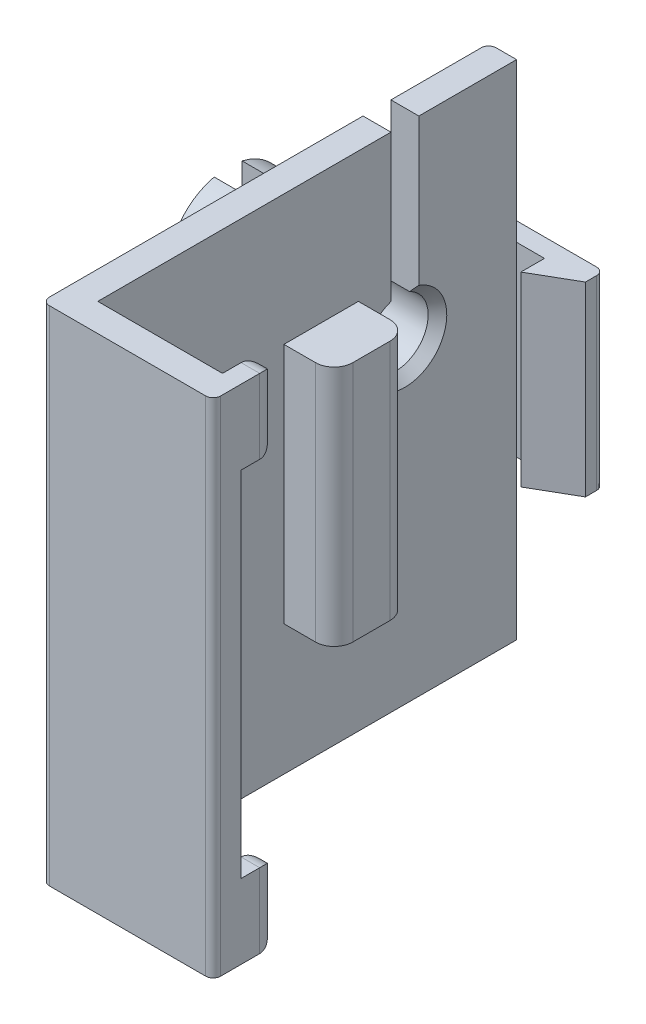
SolidWorks part; units mm, degrees
ref_plane "Front Plane" through (0, 0, 0) normal (0, 0, 1) x (1, 0, 0)
ref_plane "Top Plane" through (0, 0, 0) normal (0, 1, 0) x (1, 0, 0)
ref_plane "Right Plane" through (0, 0, 0) normal (1, 0, 0) x (0, 0, -1)
sketch "Sketch1" plane through (0, 0, 0) normal (0, 1, 0) x (1, 0, 0)
  line L0 (0, 0) -> (-2.2, 0)
  line L5 (-2.2, 0) -> (-2.2, -1.2702)
  line L6 (-2.2, -1.2702) -> (0, 0)
  dimension "D1" = 60
  dimension "D2" = 2.2
extrude "Boss-Extrude1" add sketch "Sketch1" along normal blind 5 and the other way blind 5
sketch "Sketch2" plane through (0, 0, 0) normal (0, 0, -1) x (-1, 0, 0)
  line L0 (0, 5) -> (2.2, 5) construction
  line L1 (0, -5) -> (3.7, -5)
  line L2 (0, -5) -> (0, 5)
  line L3 (0, 5) -> (3.7, 5)
  line L4 (3.7, -5) -> (3.7, 5)
  line L5 (0, -5) -> (3.7, 5) construction
  line L6 (0, 5) -> (3.7, -5) construction
  line L7 (2.2, -5) -> (2.2, 5) construction
  point P4 (1.85, 0)
  dimension "D1" = 1.5
extrude "Boss-Extrude2" add sketch "Sketch2" along normal blind 1
sketch "Sketch3" plane through (-3.7, 0, 0) normal (-1, 0, 0) x (0, 0, 1)
  line L0 (0, 0) -> (12.5427, 0) construction
  line L1 (0, -13.5) -> (22.5, -13.5)
  line L2 (0, -13.5) -> (0, 13.5)
  line L3 (0, 13.5) -> (22.5, 13.5)
  line L4 (22.5, -13.5) -> (22.5, 13.5)
  line L5 (0, -13.5) -> (22.5, 13.5) construction
  line L6 (0, 13.5) -> (22.5, -13.5) construction
  line L7 (0, -5) -> (0, 5) construction
  line L9 (0, 5) -> (-1, 5)
  line L10 (0, 5) -> (0, -5)
  line L11 (0, -5) -> (-1, -5)
  line L12 (-1, 5) -> (-1, -5)
  line L13 (0, 5) -> (-1, -5) construction
  line L14 (0, -5) -> (-1, 5) construction
  point P4 (11.25, 0)
  point P16 (-0.5, 0)
  line M6 (0, -5) -> (0, 5)
  line M7 (0, 5) -> (-1, 5)
  line M8 (-1, 5) -> (-1, -5)
  line M9 (-1, -5) -> (0, -5)
  dimension "D1" = 22.5
  dimension "D2" = 27
extrude "Boss-Extrude3" add sketch "Sketch3" along normal blind 1.5 contours L1 L4 L3 L2 M6 | M9 M6 M7 M8 region at (-3.7, 0, 11.25) region at (-3.7, 0, -0.5)
sketch "Sketch4" plane through (0, 0, 22.5) normal (0, 0, 1) x (1, 0, 0)
  line L0 (-4.45, 0) -> (4, 0) construction
  line L1 (-5.2, -13.5) -> (-3.7, -13.5)
  line L2 (-5.2, -13.5) -> (-5.2, 13.5)
  line L3 (-5.2, 13.5) -> (-3.7, 13.5)
  line L4 (-3.7, -13.5) -> (-3.7, 13.5)
  line L5 (-5.2, -13.5) -> (-3.7, 13.5) construction
  line L6 (-5.2, 13.5) -> (-3.7, -13.5) construction
  line L7 (-3.7, -13.5) -> (3, -13.5)
  line L8 (-3.7, -13.5) -> (-3.7, 13.5)
  line L9 (-3.7, 13.5) -> (3, 13.5)
  line L10 (3, -13.5) -> (3, 13.5)
  line L11 (-3.7, -13.5) -> (3, 13.5) construction
  line L12 (-3.7, 13.5) -> (3, -13.5) construction
  line L13 (4, 9.5) -> (3, 9.5)
  line L14 (3, 13.5) -> (4, 13.5)
  line L15 (3, 13.5) -> (3, -13.5)
  line L16 (3, -13.5) -> (4, -13.5)
  line L17 (4, 13.5) -> (4, -13.5)
  line L18 (3, 13.5) -> (4, -13.5) construction
  line L19 (3, -13.5) -> (4, 13.5) construction
  line L20 (4, -9.5) -> (3, -9.5)
  point P4 (-4.45, 0)
  point P11 (-0.35, 0)
  point P17 (3.5, 0)
  point P22 (0, 0)
  point P23 (0, 0)
  point P24 (0, 0)
  line M5 (-3.7, -13.5) -> (-3.7, 13.5)
  line M6 (-3.7, 13.5) -> (-5.2, 13.5)
  line M7 (-5.2, 13.5) -> (-5.2, -13.5)
  line M8 (-5.2, -13.5) -> (-3.7, -13.5)
  dimension "D4" = 4
  dimension "D2" = 6.7
  dimension "D3" = 1
extrude "Boss-Extrude4" add sketch "Sketch4" along normal blind 1.5 contours L7 L10 L9 M5 | M8 M5 M6 M7 region at (-4.45, 0, 22.5) region at (-0.35, 0, 22.5)
ref_plane "Plane1" through (0, 0, 0) normal (0, 1, 0) x (1, 0, 0)
sketch "Sketch5" plane through (-3.7, 0, 0) normal (1, 0, 0) x (0, 0, -1)
  line L5 (-10.5, -13.5) -> (-10.5, 13.5) construction
  line L7 (-12.5, 6.5) -> (-8.5, 6.5)
  line L8 (-12.5, 6.5) -> (-12.5, -6.5)
  line L9 (-12.5, -6.5) -> (-8.5, -6.5)
  line L10 (-8.5, 6.5) -> (-8.5, -6.5)
  line L11 (-12.5, 6.5) -> (-8.5, -6.5) construction
  line L12 (-12.5, -6.5) -> (-8.5, 6.5) construction
  line L14 (0, 13.5) -> (-22.5, 13.5) construction
  line L15 (0, 5) -> (0, 13.5) construction
  line L17 (0, -13.5) -> (-22.5, -13.5) construction
  point P6 (-10.5, 0)
  point P7 (-10.5, 0)
  point P12 (-10.5, 0)
  dimension "D1" = 13
  dimension "D2" = 4
  dimension "D3" = 10.5
extrude "Boss-Extrude5" add sketch "Sketch5" along normal blind 2.7 contours L8 L7 L10 L9
sketch "Sketch7" plane through (-3.7, 0, 0) normal (1, 0, 0) x (0, 0, -1)
  line L0 (0, 5) -> (0, 13.5) construction
  line L1 (0, 13.5) -> (-22.5, 13.5) construction
  line L2 (-6, 3.5) -> (-6, 13.5) construction
  line L3 (-6.75, 13.5) -> (-6.75, 5.0811)
  line L4 (-5.25, 13.5) -> (-5.25, 5.0811)
  line L5 (-6.75, 13.5) -> (-5.25, 13.5)
  circle A0 centre (-6, 3.5) radius 1.75
  circle A1 centre (-6, 3.5) radius 3.25
  line M6 (0, 13.5) -> (-22.5, 13.5)
  line M12 (-8.5, 6.5) -> (-8.5, -6.5)
  dimension "D1" = 3.5
  dimension "D6" = 1.5
  dimension "D2" = 6
  dimension "D3" = 10
  dimension "D4" = 0.75
  dimension "D5" = 1.5
extrude "Cut-Extrude1" cut sketch "Sketch7" against normal through all contours A0 | A1 L2 L5 L3 | L2 A1 L4 M6 | L2 A0 L4 A1 | A0 L2 A1 L3 region at (-3.7, 5.9573, 6.3783) region at (-3.7, 5.9573, 5.6217) region at (-3.7, 5.159, 5.6265) region at (-3.7, 10.1104, 6.3758) region at (-3.7, 10.1104, 5.6242)
extrude "Boss-Extrude6" add sketch "Sketch7<3>" against normal blind 8 from surface contours A1 M12 | L3 A1 L4 A0 M12 region at (-3.7, 5.8717, 6.8361) region at (-3.7, 3.5, 8.8032) starting at face at (-5.2, 2.8193, 5.8333)
sketch "Sketch7<3>" plane through (-3.7, 0, 0) normal (1, 0, 0) x (0, 0, -1) same geometry as "Sketch7"
ref_plane "Plane2" through (0, 0.25, 0) normal (0, -1, 0) x (-1, 0, 0)
sketch "Sketch8" plane through (0, 0.25, 0) normal (0, -1, 0) x (-1, 0, 0)
  line L0 (13.2, -2.75) -> (5.2, -2.75) construction
  line L1 (13.2, -2.75) -> (8.4, -2.75)
  line L2 (13.2, -2.75) -> (13.2, -9.25)
  line L3 (13.2, -9.25) -> (8.4, -9.25)
  line L4 (8.4, -2.75) -> (8.4, -9.25)
  line L5 (13.2, -2.75) -> (8.4, -9.25) construction
  line L6 (13.2, -9.25) -> (8.4, -2.75) construction
  line L7 (13.2, -9.25) -> (13.2, -2.75) construction
  point P4 (10.8, -6)
  dimension "D1" = 4.8
ref_axis "Axis1" through (-13.2, 3.5, 6) along (1, 0, 0)
ref_plane "Plane3" through (0, 3.5, 0) normal (0, 1, 0) x (1, 0, 0)
extrude "Cut-Extrude2" cut sketch "Sketch8" against normal up to surface (3.25 mm away) up to plane "Plane3"
fillet "Fillet4" radius 1 2 edges at (-1, 0, 12.5) (-1, 0, 8.5)
chamfer "Chamfer1" distance 2 angle 45 2 edges at (-8.4, 3.5, 8.5) (-8.4, 3.5, 3.5)
chamfer "Chamfer3" distance 0.5 angle 45 1 edges at (-3.7, 1.75, 6)
extrude "Boss-Extrude7" add sketch "Sketch4<3>" against normal blind 2 separate body contours L17 L20 L10 L16 | L17 L14 L10 L13 region at (3.5, -11.5, 22.5) region at (3.5, 11.5, 22.5)
sketch "Sketch4<3>" plane through (0, 0, 22.5) normal (0, 0, 1) x (1, 0, 0) same geometry as "Sketch4"
extrude "Boss-Extrude8" add sketch "Sketch4<4>" along normal up to surface (1.5 mm away) contours L20 L17 L13 L15 | L17 L20 L10 L16 | L17 L14 L10 L13 region at (3.5, -11.5, 22.5) region at (3.5, 11.5, 22.5) region at (3.5, 0, 22.5) up to face at (-1.1, 0, 24)
sketch "Sketch4<4>" plane through (0, 0, 22.5) normal (0, 0, 1) x (1, 0, 0) same geometry as "Sketch4"
fillet "Fillet6" radius 1 8 edges at (3.5, -9.5, 20.5) (3, -11.5, 20.5) (3.5, -13.5, 20.5) (4, -11.5, 20.5) (3.5, 13.5, 20.5) (3, 11.5, 20.5) (3.5, 9.5, 20.5) (4, 11.5, 20.5)
fillet "Fillet8" radius 0.4 6 edges at (0, 0, -1) (-5.2, 9.25, 0) (-5.2, -9.25, 0) (-5.2, 0, -1) (-5.2, 0, 24) (4, 0, 24)
equation "\"WallThick\"= 1.2'thickness of wall for printer"
equation "\"dHole\"= 3.3'diameter of screw hole"
equation "\"dCable\"= 1.5"
equation "\"FillHole\"= 8'Height of fill hole to seal with hot glue"
equation "\"D1@Sketch8\"=0.6*\"FillHole\""
equation "\"D1@Boss-Extrude6\"=\"FillHole\""
